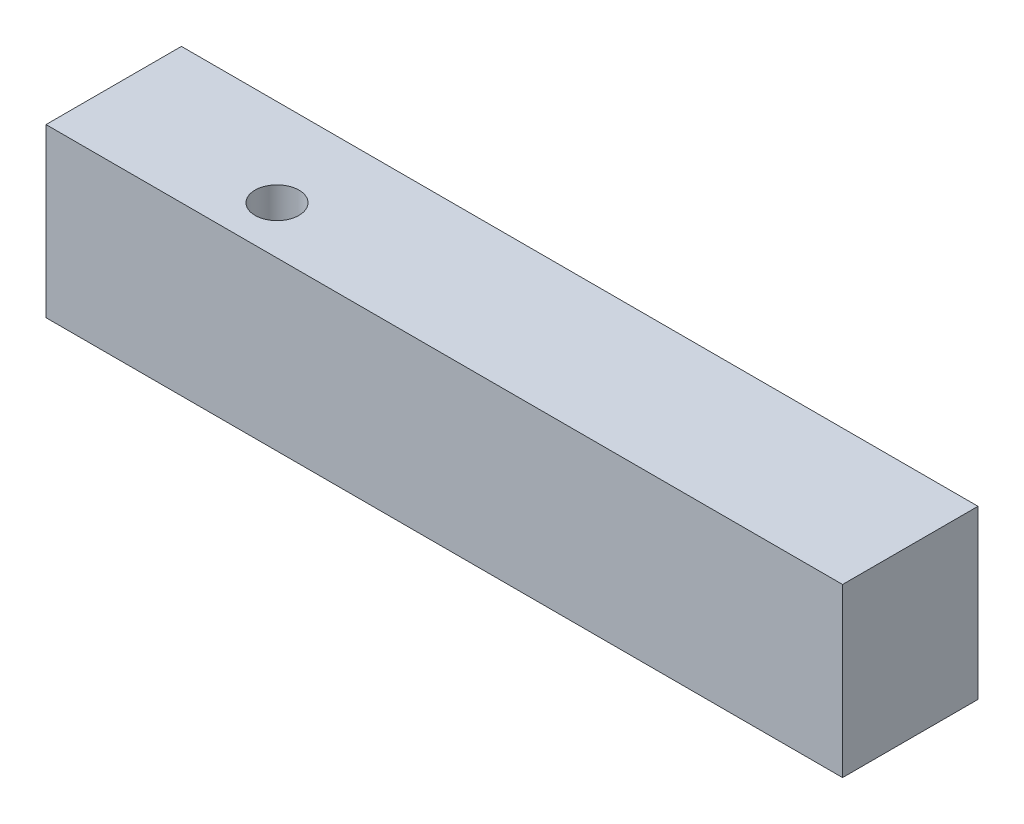
SolidWorks part; units mm, degrees
ref_plane "Front Plane" through (0, 0, 0) normal (0, 0, 1) x (1, 0, 0)
ref_plane "Top Plane" through (0, 0, 0) normal (0, 1, 0) x (1, 0, 0)
ref_plane "Right Plane" through (0, 0, 0) normal (1, 0, 0) x (0, 0, -1)
sketch "Sketch1" plane through (0, 0, 0) normal (0, 0, 1) x (1, 0, 0)
  line L1 (-4.7947, 2.3825) -> (20.6053, 2.3825)
  line L2 (-4.7947, 2.3825) -> (-4.7947, -2.9515)
  line L3 (-4.7947, -2.9515) -> (20.6053, -2.9515)
  line L4 (20.6053, 2.3825) -> (20.6053, -2.9515)
  dimension "D1" = 5.334
  dimension "D2" = 25.4
extrude "Boss-Extrude1" add sketch "Sketch1" along normal blind 4.318
sketch "Sketch2" plane through (0, 2.3825, 0) normal (0, 1, 0) x (1, 0, 0)
  line L1 (-4.7947, -4.318) -> (-4.7947, 0) construction
  line L2 (20.6053, 0) -> (-4.7947, 0) construction
  circle A0 centre (1.0473, -2.794) radius 0.7
  dimension "D1" = 2.794
  dimension "D2" = 5.842
  dimension "D3" = 1.4
extrude "Cut-Extrude2" cut sketch "Sketch2" against normal through all
equation "\"MDF\"= .21in"
equation "\"Foamcore\"= .13in"
equation "\"Gmaterial\"= \"MDF\""
equation "\"D1@Sketch1\"=\"MDF\""
